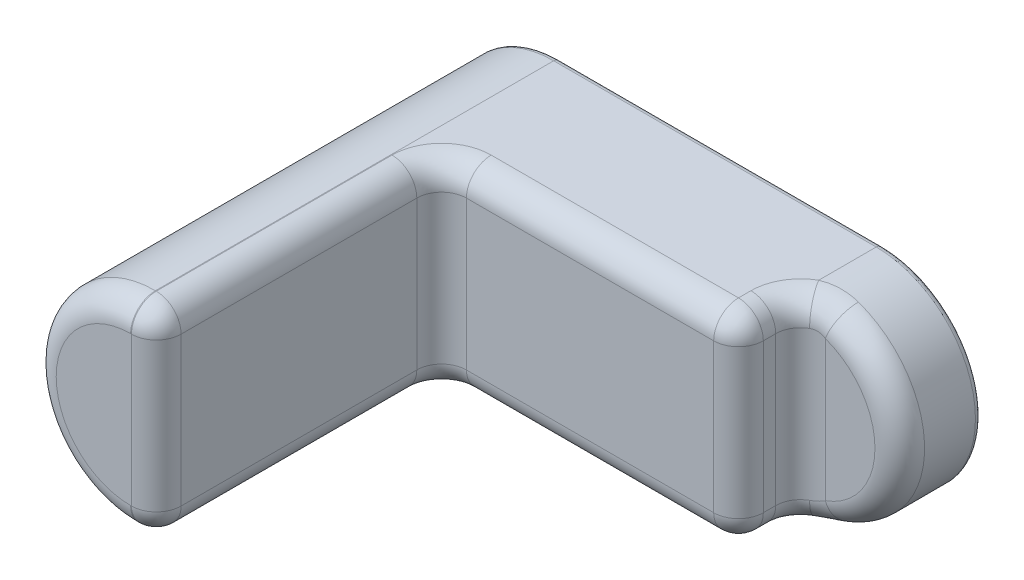
SolidWorks part; units mm, degrees
ref_plane "Alzado" through (0, 0, 0) normal (0, 0, 1) x (1, 0, 0)
ref_plane "Planta" through (0, 0, 0) normal (0, 1, 0) x (1, 0, 0)
ref_plane "Vista lateral" through (0, 0, 0) normal (1, 0, 0) x (0, 0, -1)
sketch "Croquis1" plane through (0, 0, 0) normal (0, 0, 1) x (1, 0, 0)
  line L0 (0, 0) -> (130, 0) construction
  line L1 (0, 40) -> (130, 40)
  line L2 (0, -40) -> (130, -40)
  arc A0 (0, 40) -> (0, -40) centre (0, 0) ccw
  arc A1 (130, -40) -> (130, 40) centre (130, 0) ccw
  dimension "D1" = 80
  dimension "D2" = 80
  dimension "D3" = 130
extrude "Saliente-Extruir1" add sketch "Croquis1" along normal blind 33
sketch "Croquis2" plane through (0, 0, 33) normal (0, 0, 1) x (1, 0, 0)
  line L1 (0, 40) -> (10.3359, 40)
  line L2 (130, 40) -> (0, 40) construction
  line L3 (10.3359, 40) -> (10.3359, -40)
  line L4 (0, -40) -> (130, -40) construction
  line L5 (10.3359, -40) -> (0, -40)
  arc A0 (0, 40) -> (0, -40) centre (0, 0) ccw
extrude "Saliente-Extruir2" add sketch "Croquis2" along normal blind 140
sketch "Croquis3" plane through (0, 0, 33) normal (0, 0, 1) x (1, 0, 0)
  line L1 (0, 40) -> (130, 40)
  line L2 (0, 40) -> (0, -40)
  line L3 (0, -40) -> (130, -40)
  line L4 (130, 40) -> (130, -40)
extrude "Saliente-Extruir3" add sketch "Croquis3" along normal blind 25
fillet "Redondeo1" radius 10 14 edges at (-40, 0, 173) (170, 0, 33) (130, -40, 45.5) (130, 40, 45.5) (130, 0, 33) (70.1679, 40, 58) (130, 0, 58) (70.1679, -40, 58) (10.3359, 40, 115.5) (10.3359, -40, 115.5) (5.1679, 40, 173) (10.3359, 0, 173) (5.1679, -40, 173) (10.3359, 0, 58)
fillet "Redondeo2" radius 2.5 4 edges at (65, -40, 0) (170, 0, 0) (65, 40, 0) (-40, 0, 0)
sketch "Croquis4" plane through (0, 0, 0) normal (0, 0, -1) x (-1, 0, 0)
  circle A0 centre (0, 0) radius 4
  dimension "D1" = 8
extrude "Cortar-Extruir1" cut sketch "Croquis4" against normal blind 165
sketch "Croquis5" plane through (0, 0, 0) normal (0, 0, -1) x (-1, 0, 0)
  line L0 (-130, 37.5) -> (-130, -37.5) construction
  circle A0 centre (-130, 0) radius 30
  dimension "D1" = 60
extrude "Cortar-Extruir2" cut sketch "Croquis5" against normal blind 20
